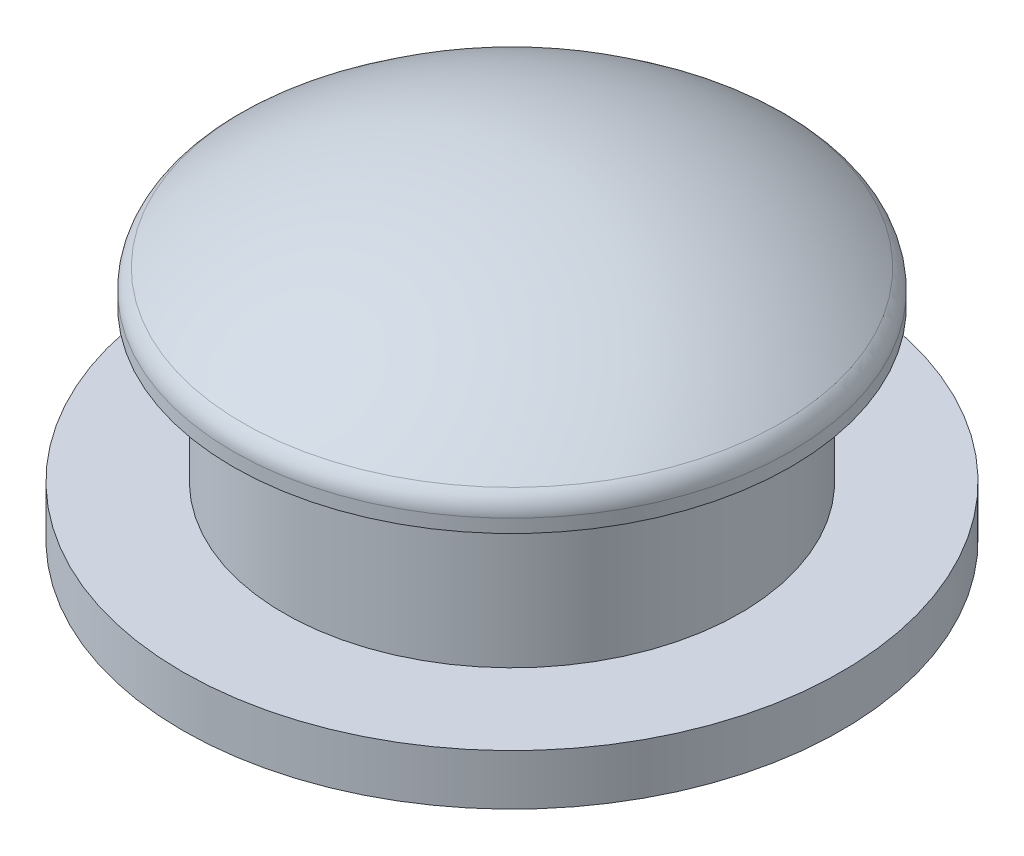
SolidWorks part; units mm, degrees
material "Alliage 7079"
ref_plane "Face" through (0, 0, 0) normal (0, 0, 1) x (1, 0, 0)
ref_plane "Dessus" through (0, 0, 0) normal (0, 1, 0) x (1, 0, 0)
ref_plane "Droite" through (0, 0, 0) normal (1, 0, 0) x (0, 0, -1)
sketch "Esquisse1" plane through (0, 0, 0) normal (0, 0, 1) x (1, 0, 0)
  line L0 (0, 0) -> (0, 4.5)
  line L1 (0, 4.5) -> (5.5, 4.5)
  line L2 (5.5, 4.5) -> (5.5, 4)
  line L3 (5.5, 4) -> (4.5, 4)
  line L4 (4.5, 4) -> (4.5, 1)
  line L5 (4.5, 1) -> (6.5, 1)
  line L6 (6.5, 1) -> (6.5, 0)
  line L7 (6.5, 0) -> (0, 0)
  dimension "D1" = 5.5
  dimension "D2" = 4.5
  dimension "D3" = 6.5
  dimension "D4" = 0.5
  dimension "D5" = 3
  dimension "D6" = 1
revolve "Révolution1" add sketch "Esquisse1" angle 360 about L0
dome "Dôme1" faces to dome 1 distance 2 reverse direction no elliptical dome no face at (0, 4.5, -5.5) parameters "D1"=2
fillet "Congé1" radius 0.5 1 edges at (0, 4.5, -5.5)
shell "Coque1" thickness 1 removed face at (0, 0, -6.5)
fillet "Congé2" radius 2 1 edges at (0, 0, 3.5)
